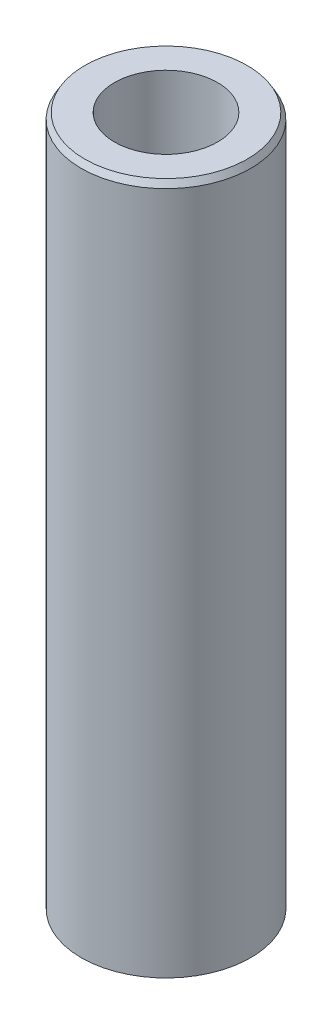
SolidWorks part; units mm, degrees
ref_plane "Front Plane" through (0, 0, 0) normal (0, 0, 1) x (1, 0, 0)
ref_plane "Top Plane" through (0, 0, 0) normal (0, 1, 0) x (1, 0, 0)
ref_plane "Right Plane" through (0, 0, 0) normal (1, 0, 0) x (0, 0, -1)
sketch "Sketch1" plane through (0, 0, 0) normal (0, 1, 0) x (1, 0, 0)
  circle A0 centre (0, 0) radius 35
  dimension "SHAFT_OD" = 70
extrude "Boss-Extrude1" add sketch "Sketch1" along normal blind 286.2202
sketch "Sketch2" plane through (0, 0, 0) normal (0, 1, 0) x (1, 0, 0)
  circle A0 centre (0, 0) radius 21.2832
  dimension "BORE_D" = 42.5663
extrude "Cut-Extrude1" cut sketch "Sketch2" along normal through all
chamfer "Chamfer1" distance 2.5614 angle 30 2 edges at (0, 286.2202, 35) (0, 0, 35) first distance on face at (0, 286.2202, 35) first distance on face at (0, 0, 21.2832)
